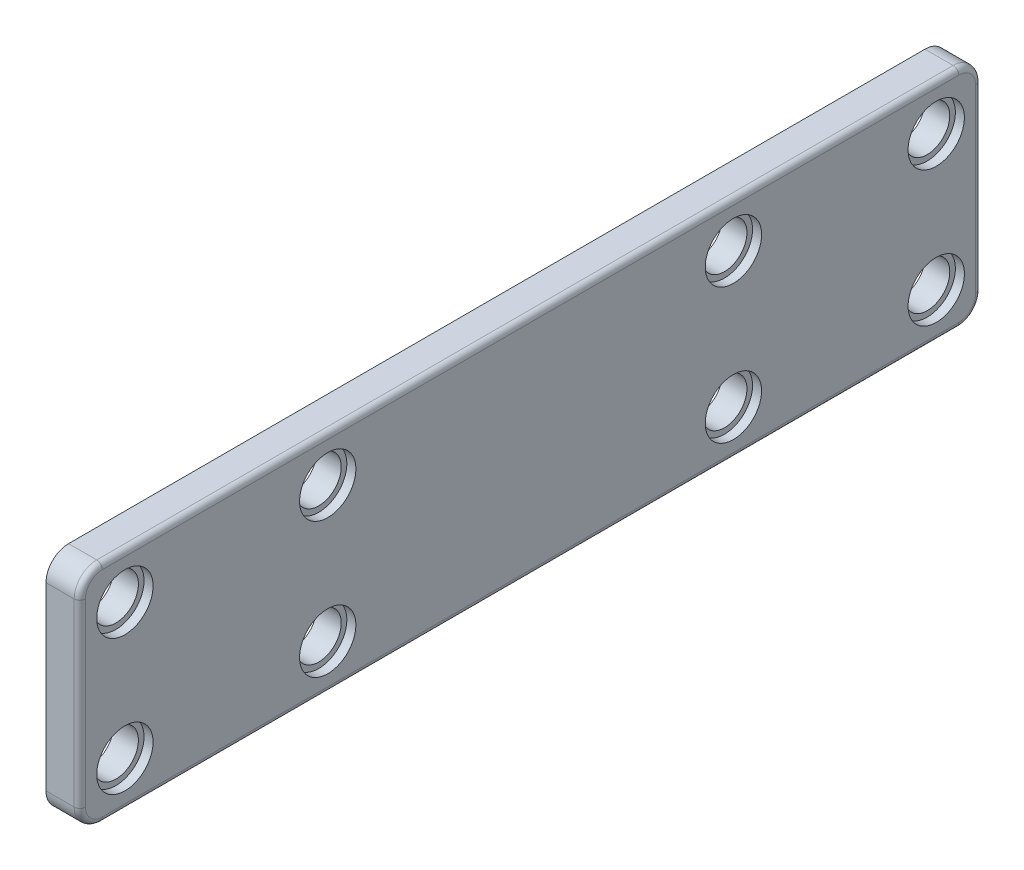
SolidWorks part; units mm, degrees
ref_plane "Front Plane" through (0, 0, 0) normal (0, 0, 1) x (1, 0, 0)
ref_plane "Top Plane" through (0, 0, 0) normal (0, 1, 0) x (1, 0, 0)
ref_plane "Right Plane" through (0, 0, 0) normal (1, 0, 0) x (0, 0, -1)
sketch "Sketch2" plane through (0, 0, 0) normal (0, 0, 1) x (1, 0, 0)
  line L1 (-1.5, -10) -> (1.5, -10)
  line L2 (-1.5, -10) -> (-1.5, 10)
  line L3 (-1.5, 10) -> (1.5, 10)
  line L4 (1.5, -10) -> (1.5, 10)
  line L5 (-1.5, -10) -> (1.5, 10) construction
  line L6 (-1.5, 10) -> (1.5, -10) construction
  point P0 (0, 0)
  dimension "D1" = 20
  dimension "D2" = 3
extrude "Boss-Extrude2" add sketch "Sketch2" along normal blind 80
fillet "Fillet3" radius 2 1 edges at (0, 10, 80)
fillet "Fillet4" radius 2 1 edges at (0, -10, 80)
fillet "Fillet5" radius 2 1 edges at (0, 10, 0)
fillet "Fillet6" radius 2 1 edges at (0, -10, 0)
sketch "Sketch3" plane through (1.5, 0, 0) normal (1, 0, 0) x (0, 0, -1)
  line L0 (-86.0874, 0) -> (15.1847, 0) construction
  line L2 (-80, -8) -> (-80, 8) construction
  line L3 (-40, 10) -> (-40, -20.1361) construction
  line L4 (-78, 10) -> (-2, 10) construction
  point P3 (-76, 6)
  dimension "D1" = 6
  dimension "D2" = 4
hole_wizard "CBORE for M5 Hex Head Bolt1" positions "Sketch5" profile "Sketch4" counterbore size "M5" standard "DIN"
sketch "Sketch5" plane through (1.5, 0, 0) normal (1, 0, 0) x (0, 0, -1)
  point P0 (-76, 6)
sketch "Sketch4" plane through (1.5, 6, 76) normal (0, 1, 0) x (0, 0, -1)
  line L0 (0, 0) -> (0, 5.1781)
  line L1 (0, 5.1781) -> (2, 4)
  line L2 (2, 4) -> (2, 0.8)
  line L3 (2, 0.8) -> (2.5, 0.8)
  line L4 (2.5, 0.8) -> (2.5, 0)
  line L5 (2.5, 0) -> (0, 0)
  line L10 (0, 5.1781) -> (-2, 4) construction
  line L11 (0, -6.35) -> (0, 107.95) construction
  dimension "Hole Dia." = 4
  dimension "Hole Depth" = 4
  dimension "C'Bore Dia." = 5
  dimension "C'Bore Depth" = 0.8
  dimension "Drill Angle" = 119
pattern_linear "LPattern1" count 2 spacing 18 along (0, 0, -1) count 2 spacing 12 along (0, -1, 0) of "CBORE for M5 Hex Head Bolt1"
ref_plane "Plane1" through (0, 0, 40) normal (0, 0, 1) x (0, -1, 0)
mirror "Mirror16" about plane through (0, 0, 40) normal (0, 0, 1) of "LPattern1", "CBORE for M5 Hex Head Bolt1"
fillet "Fillet7" radius 0.5 8 edges at (1.5, -9.4142, 79.4142) (1.5, 0, 80) (1.5, 9.4142, 79.4142) (1.5, 10, 40) (1.5, 9.4142, 0.5858) (1.5, 0, 0) (1.5, -9.4142, 0.5858) (1.5, -10, 40)
